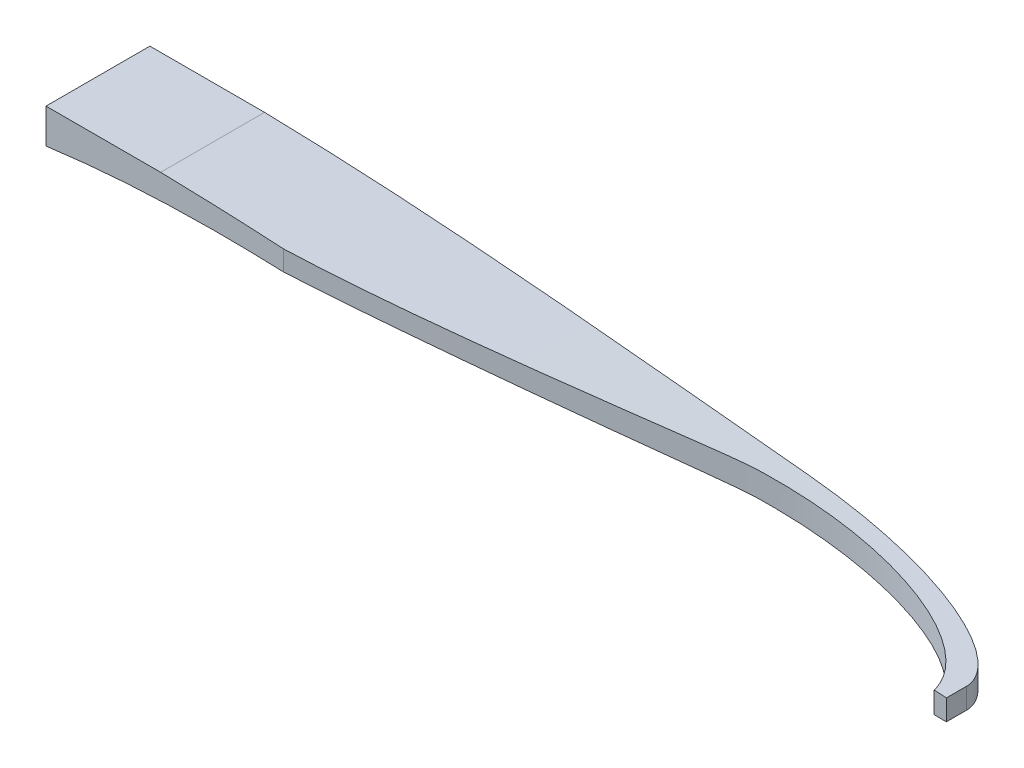
SolidWorks part; units mm, degrees
ref_plane "Front Plane" through (0, 0, 0) normal (0, 0, 1) x (1, 0, 0)
ref_plane "Top Plane" through (0, 0, 0) normal (0, 1, 0) x (1, 0, 0)
ref_plane "Right Plane" through (0, 0, 0) normal (1, 0, 0) x (0, 0, -1)
sketch "Sketch1" plane through (0, 0, 0) normal (0, 1, 0) x (1, 0, 0)
  line L1 (0, 0) -> (165.1, 0)
  line L2 (0, 0) -> (0, 19.05)
  line L3 (0, 19.05) -> (165.1, 19.05)
  line L4 (165.1, 0) -> (165.1, 19.05)
  dimension "D1" = 165.1
  dimension "D2" = 19.05
extrude "Boss-Extrude1" add sketch "Sketch1" along normal blind 15.24
sketch "Sketch3" plane through (0, 0, -19.05) normal (0, 0, -1) x (-1, 0, 0)
  line L0 (0, 15.24) -> (0, 0) construction
  line L1 (-165.1, 15.24) -> (-165.1, 0) construction
  spline S0 degree 3 poles (0, 8.89) (-55.6105, 16.425) (-109.8023, 0.4666) (-165.1, 0) knots 0 0 0 0 1 1 1 1
  spline S1 degree 3 poles (0, 15.24) (-55.3652, 16.4782) (-110.0248, 7.2673) (-165.1, 3.81) knots 0 0 0 0 1 1 1 1
  point P6 (-65.2384, 9.2386)
  line M1 (-165.1, 0) -> (0, 0)
  line M2 (0, 0) -> (0, 15.24)
  line M3 (0, 15.24) -> (-165.1, 15.24)
  line M4 (-165.1, 15.24) -> (-165.1, 0)
  dimension "D1" = 6.35
  dimension "D2" = 3.81
  dimension "D3" = 4.445
  dimension "D4" = 3.6908
extrude "Cut-Extrude1" cut sketch "Sketch3" against normal through all contours S0 M2 M1 | S1 M3 M4 region at (55.2591, 4.3867, -19.05) region at (121.9044, 11.3739, -19.05)
sketch "Sketch4" plane through (0, 15.24, 0) normal (0, 1, 0) x (1, 0, 0)
  line L0 (21.0306, 19.05) -> (0, 19.05) construction
  line L1 (21.0306, 0) -> (165.1, 0) construction
  line L2 (165.1, 0) -> (165.1, 19.05) construction
  line L3 (32.9054, -0.4997) -> (162.9821, -0.4997)
  line L4 (165.1, 3.6588) -> (165.1, 19.05)
  line L5 (165.1, 19.05) -> (120.8556, 19.05)
  spline S0 degree 3 poles (32.9054, -0.4997) (58.544, -0.7303) (108.2301, 13.7439) (117.3285, 14.9152) (141.3741, 17.3498) (161.2826, 9.1598) (162.9821, -0.4997) knots 0 0 0 0 0.232815 0.263033 0.297827 1 1 1 1
  spline S1 degree 3 poles (120.8556, 19.05) (147.3947, 18.9666) (165.098, 10.4831) (165.1, 3.6588) knots 0 0 0 0 1 1 1 1
  point P4 (0, 0)
  point P10 (120.8556, 19.05)
  point P11 (0, 0)
  point P12 (0, 0)
  point P13 (162.9821, 0.8263)
  point P16 (116.7955, 14.8387)
  point P20 (0, 0)
  line M2 (21.0306, 19.05) -> (0, 19.05)
  line M4 (0, 0) -> (21.0306, 0)
  dimension "D1" = 3.81
extrude "Cut-Extrude2" cut sketch "Sketch4" against normal blind 19.05 contours S0 M4 | S1 M2 region at (116.1488, 15.24, -5.5987) region at (155.0338, 15.24, -15.4762)
